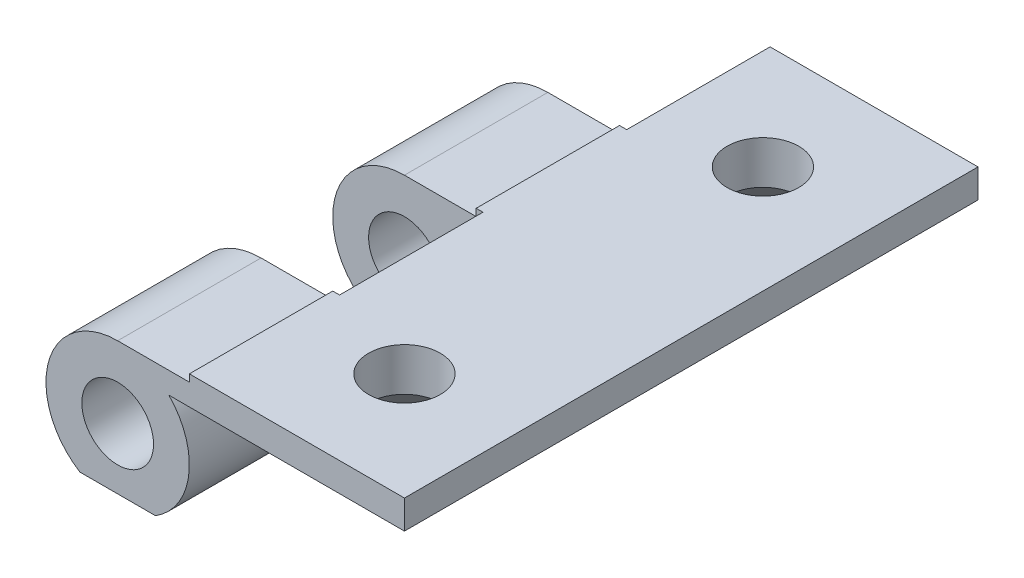
SolidWorks part; units mm, degrees
ref_plane "Ön Düzlem" through (0, 0, 0) normal (0, 0, 1) x (1, 0, 0)
ref_plane "Üst Düzlem" through (0, 0, 0) normal (0, 1, 0) x (1, 0, 0)
ref_plane "Sağ Düzlem" through (0, 0, 0) normal (1, 0, 0) x (0, 0, -1)
sketch "Çizim1" plane through (0, 0, 0) normal (0, 0, 1) x (1, 0, 0)
  line L0 (0, 5) -> (5, 5)
  line L1 (20, 5) -> (20, 0.5)
  line L2 (20, 0.5) -> (4.9749, 0.5)
  line L3 (20, 5) -> (20, 5.5)
  line L4 (20, 5.5) -> (5, 5.5)
  line L5 (5, 5.5) -> (5, 5)
  arc A0 (0, 5) -> (4.9749, 0.5) centre (0, 0) ccw
  circle A1 centre (0, 0) radius 2.5
  dimension "D1" = 10
  dimension "D7" = 5
  dimension "D2" = 20
  dimension "D3" = 4.5
  dimension "D4" = 0.5
  dimension "D5" = 15
  dimension "D6" = 5.5
extrude "Yükseklik-Ekstrüzyon1" add sketch "Çizim1" along normal blind 40
sketch "Çizim2" plane through (0, 0, 40) normal (0, 0, 1) x (1, 0, 0)
  line L0 (-6.3368, -4.25) -> (12.4224, -4.25)
  circle A1 centre (0, 0) radius 2.5 construction
  dimension "D1" = 4.25
extrude "Kes-Ekstrüzyon1" cut sketch "Çizim2" against normal through all and the other way through all flip side to cut
sketch "Çizim3" plane through (0, -4.25, 0) normal (0, -1, 0) x (1, 0, 0)
  line L1 (-5, 30) -> (5, 30)
  line L2 (-5, 30) -> (-5, 20)
  line L3 (-5, 20) -> (5, 20)
  line L4 (5, 30) -> (5, 20)
  line L6 (2.6339, 40) -> (-2.6339, 40) construction
  line L7 (5, 0) -> (-5, 0)
  line L8 (5, 0) -> (5, 10)
  line L9 (5, 10) -> (-5, 10)
  line L10 (-5, 0) -> (-5, 10)
  line L11 (20, 40) -> (20, 0) construction
  dimension "D1" = 10
  dimension "D2" = 10
  dimension "D3" = 10
  dimension "D4" = 10
  dimension "D5" = 10
  dimension "D6" = 15
  dimension "D7" = 15
  dimension "D8" = 10
extrude "Kes-Ekstrüzyon2" cut sketch "Çizim3" against normal through all
sketch "Çizim4" plane through (0, 0.5, 0) normal (0, -1, 0) x (1, 0, 0)
  line L1 (5, 0) -> (20, 0) construction
  line L2 (4.9749, 30) -> (5.4749, 30)
  line L3 (4.9749, 30) -> (4.9749, 20)
  line L4 (4.9749, 20) -> (5.4749, 20)
  line L5 (5.4749, 30) -> (5.4749, 20)
  line L6 (5, 10) -> (5.5, 10)
  line L7 (5, 10) -> (5, 0)
  line L8 (5, 0) -> (5.5, 0)
  line L11 (5.5, 10) -> (5.5, 0)
  dimension "D1" = 0.5
  dimension "D2" = 10
  dimension "D3" = 0.5
sketch "Çizim5" plane through (0, 0.5, 0) normal (0, -1, 0) x (1, 0, 0)
  line L2 (20, 20) -> (42.6437, 20) construction
  line L3 (5, 0) -> (20, 0) construction
  line L4 (20, 40) -> (20, 0) construction
  circle A0 centre (12.5, 7.5) radius 2.5
  circle A1 centre (12.5, 32.5) radius 2.5
  dimension "D1" = 7.5
  dimension "D2" = 7.5
  dimension "D3" = 5
extrude "Kes-Ekstrüzyon4" cut sketch "Çizim5" against normal through all
chamfer "Pah1" distance 3 angle 45 3 edges at (12.5, 0.5, 0) (20, 0.5, 20) (12.4875, 0.5, 40)
extrude "Kes-Ekstrüzyon5" cut sketch "Çizim4" against normal through all
chamfer "Pah2" distance 2 angle 45 2 edges at (12.5, 0.5, 5) (12.5, 0.5, 35)
